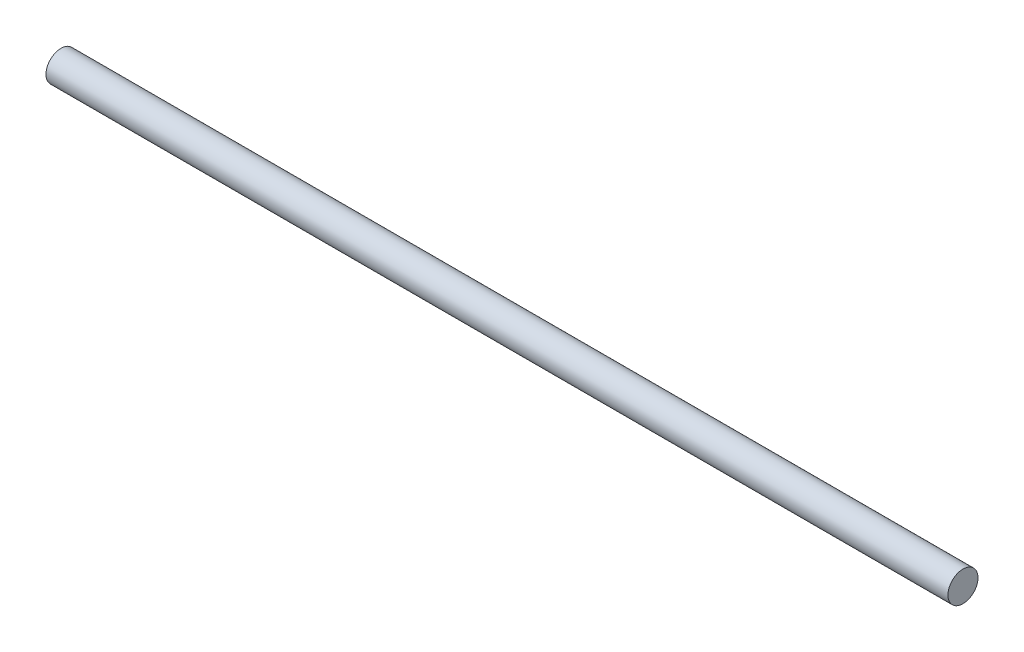
SolidWorks part; units mm, degrees
ref_plane "Front Plane" through (0, 0, 0) normal (0, 0, 1) x (1, 0, 0)
ref_plane "Top Plane" through (0, 0, 0) normal (0, 1, 0) x (1, 0, 0)
ref_plane "Right Plane" through (0, 0, 0) normal (1, 0, 0) x (0, 0, -1)
sketch "Sketch1" plane through (0, 0, 0) normal (1, 0, 0) x (0, 0, -1)
  circle A0 centre (0, 0) radius 1
  dimension "D1" = 2
extrude "Boss-Extrude1" add sketch "Sketch1" along normal blind 30 and the other way blind 30
